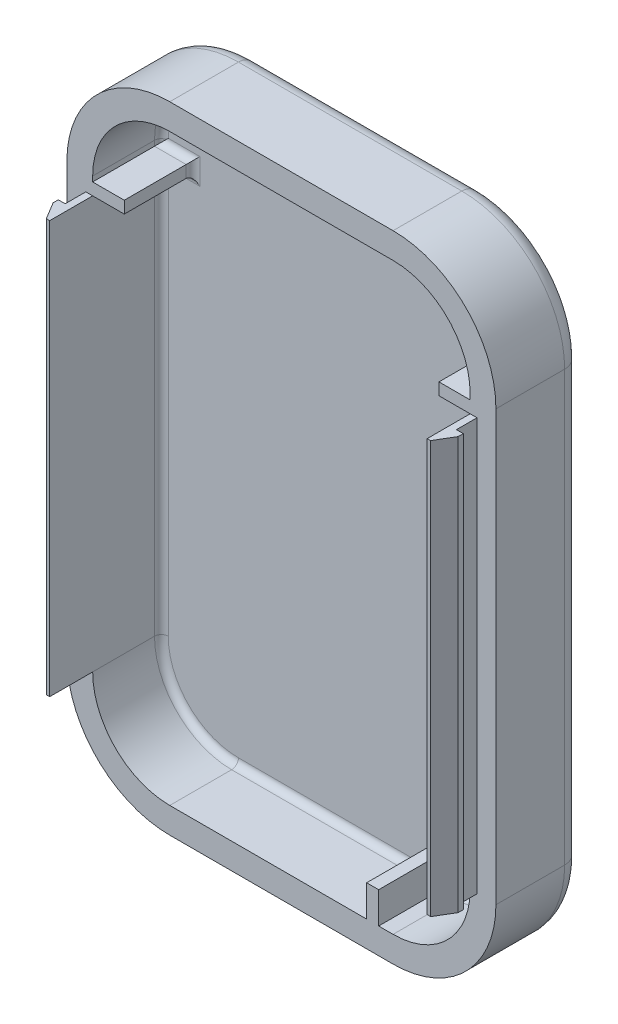
SolidWorks part; units mm, degrees
ref_plane "Front Plane" through (0, 0, 0) normal (0, 0, 1) x (1, 0, 0)
ref_plane "Top Plane" through (0, 0, 0) normal (0, 1, 0) x (1, 0, 0)
ref_plane "Right Plane" through (0, 0, 0) normal (1, 0, 0) x (0, 0, -1)
sketch "Sketch1" plane through (0, 0, 25.9804) normal (0, 0, -1) x (-1, 0, 0)
  line L15 (-18.3299, 29.3735) -> (-16.5134, 29.3735)
  line L16 (-16.5134, 29.3735) -> (-16.5134, 30.0735)
  line L17 (-16.5134, 30.0735) -> (-18.3299, 30.0735)
  line L18 (-16.2134, 29.0735) -> (-17.8299, 29.0735) construction
  line L19 (-16.2134, 30.3735) -> (-16.2134, 29.0735) construction
  line L20 (-17.8299, 30.3735) -> (-16.2134, 30.3735) construction
  line L21 (-18.3299, 30.0735) -> (-18.3299, 30.3735)
  line L22 (3.6447, 29.3735) -> (1.8044, 29.3735)
  line L23 (1.8044, 29.3735) -> (1.8044, 30.0735)
  line L24 (1.8044, 30.0735) -> (3.6447, 30.0735)
  line L25 (1.5044, 29.0735) -> (1.5044, 30.3735) construction
  line L26 (3.1447, 29.0735) -> (1.5044, 29.0735) construction
  line L27 (1.5044, 30.3735) -> (3.1447, 30.3735) construction
  line L28 (3.6447, 30.0735) -> (3.6447, 30.3735)
  line L29 (2.0044, 29.5735) -> (2.0044, 29.8735)
  line L30 (2.0044, 29.8735) -> (3.6168, 29.8735)
  line L31 (-0.8426, 34.8608) -> (-13.8426, 34.8608)
  line L32 (-18.302, 29.8735) -> (-16.7134, 29.8735)
  line L33 (-16.7134, 29.8735) -> (-16.7134, 29.5735)
  line L34 (-16.7134, 29.5735) -> (-18.3299, 29.5735)
  line L35 (-18.3299, 29.5735) -> (-18.3299, 5.3734)
  line L36 (-13.8426, 0.8861) -> (-12.8028, 0.8861)
  line L37 (-12.8028, 0.8861) -> (-12.8028, 2.5175)
  line L38 (-12.8028, 2.5175) -> (-12.5028, 2.5175)
  line L39 (-12.5028, 2.5175) -> (-12.5028, 0.8861)
  line L40 (-12.5028, 0.8861) -> (-0.8426, 0.8861)
  line L41 (3.6447, 5.3734) -> (3.6447, 29.5735)
  line L42 (3.6447, 29.5735) -> (2.0044, 29.5735)
  line L45 (-0.8426, 34.8608) -> (-13.8426, 34.8608)
  line L49 (-18.3299, 29.3735) -> (-18.3299, 5.3734)
  line L50 (-13.8426, 0.8861) -> (-13.0028, 0.8861)
  line L54 (-12.3028, 0.8861) -> (-0.8426, 0.8861)
  line L55 (3.6447, 5.3734) -> (3.6447, 29.3735)
  line L57 (-12.3028, 0.8861) -> (-12.3028, 2.7175)
  line L58 (-12.3028, 2.7175) -> (-13.0028, 2.7175)
  line L59 (-13.0028, 2.7175) -> (-13.0028, 0.8861)
  line L60 (-13.3028, 3.0175) -> (-12.0028, 3.0175) construction
  line L61 (-13.3028, 1.3861) -> (-13.3028, 3.0175) construction
  line L62 (-12.0028, 3.0175) -> (-12.0028, 1.3861) construction
  line L66 (-0.8426, 36.3608) -> (-13.8426, 36.3608)
  line L67 (-0.8426, 36.3608) -> (-13.8426, 36.3608)
  line L69 (5.1447, 5.3734) -> (5.1447, 29.0735)
  line L70 (5.1447, 5.3734) -> (5.1447, 30.3735)
  line L72 (-19.8299, 29.0735) -> (-19.8299, 5.3734)
  line L73 (-19.8299, 30.3735) -> (-19.8299, 5.3734)
  line L75 (-12.0028, -0.6139) -> (-0.8426, -0.6139)
  line L76 (-13.8426, -0.6139) -> (-0.8426, -0.6139)
  arc A6 (-13.8426, 36.3608) -> (-19.8299, 30.3735) centre (-13.8426, 30.3735) ccw
  arc A7 (-13.8426, 36.3608) -> (-19.8299, 30.3735) centre (-13.8426, 30.3735) ccw
  arc A8 (3.6168, 29.8735) -> (-0.8426, 34.8608) centre (-0.8426, 30.3735) ccw
  arc A9 (-13.8426, 34.8608) -> (-18.302, 29.8735) centre (-13.8426, 30.3735) ccw
  arc A10 (-18.3299, 5.3734) -> (-13.8426, 0.8861) centre (-13.8426, 5.3734) ccw
  arc A11 (-0.8426, 0.8861) -> (3.6447, 5.3734) centre (-0.8426, 5.3734) ccw
  arc A12 (3.6447, 30.3735) -> (-0.8426, 34.8608) centre (-0.8426, 30.3735) ccw
  arc A13 (-13.8426, 34.8608) -> (-18.3299, 30.3735) centre (-13.8426, 30.3735) ccw
  arc A14 (-18.3299, 5.3734) -> (-13.8426, 0.8861) centre (-13.8426, 5.3734) ccw
  arc A15 (-0.8426, 0.8861) -> (3.6447, 5.3734) centre (-0.8426, 5.3734) ccw
  arc A17 (5.1447, 30.3735) -> (-0.8426, 36.3608) centre (-0.8426, 30.3735) ccw
  arc A18 (5.1447, 30.3735) -> (-0.8426, 36.3608) centre (-0.8426, 30.3735) ccw
  arc A20 (-19.8299, 5.3734) -> (-13.8426, -0.6139) centre (-13.8426, 5.3734) ccw
  arc A21 (-19.8299, 5.3734) -> (-13.8426, -0.6139) centre (-13.8426, 5.3734) ccw
  arc A23 (-0.8426, -0.6139) -> (5.1447, 5.3734) centre (-0.8426, 5.3734) ccw
  arc A24 (-0.8426, -0.6139) -> (5.1447, 5.3734) centre (-0.8426, 5.3734) ccw
  dimension "D2" = 0.3
  dimension "D3" = 0.3
  dimension "D4" = 0.3
  dimension "D5" = 0.3
  dimension "D6" = 0.3
  dimension "D7" = 0.3
  dimension "D8" = 0.3
  dimension "D9" = 0.3
  dimension "D10" = 0.3
  dimension "D1" = 0.5
  dimension "D11" = 2
  dimension "D12" = 2
  dimension "D13" = 2
  dimension "D14" = 2
  dimension "D15" = 2
  dimension "D16" = 2
  dimension "D17" = 2
  dimension "D18" = 2
extrude "Boss-Extrude1" add sketch "Sketch1" along normal blind 4
sketch "Sketch2" plane through (0, 0, 21.9804) normal (0, 0, -1) x (-1, 0, 0)
  line L0 (-19.8299, 30.3735) -> (-19.8299, 5.3734) construction
  line L1 (-13.8426, -0.6139) -> (-0.8426, -0.6139) construction
  line L2 (5.1447, 5.3734) -> (5.1447, 30.3735) construction
  line L3 (-0.8426, 36.3608) -> (-13.8426, 36.3608) construction
  line L4 (-19.8299, 30.3735) -> (-19.8299, 5.3734)
  line L5 (-13.8426, -0.6139) -> (-0.8426, -0.6139)
  line L6 (5.1447, 5.3734) -> (5.1447, 30.3735)
  line L7 (-0.8426, 36.3608) -> (-13.8426, 36.3608)
  arc A0 (-19.8299, 5.3734) -> (-13.8426, -0.6139) centre (-13.8426, 5.3734) ccw construction
  arc A1 (-0.8426, -0.6139) -> (5.1447, 5.3734) centre (-0.8426, 5.3734) ccw construction
  arc A2 (5.1447, 30.3735) -> (-0.8426, 36.3608) centre (-0.8426, 30.3735) ccw construction
  arc A3 (-13.8426, 36.3608) -> (-19.8299, 30.3735) centre (-13.8426, 30.3735) ccw construction
  arc A4 (-19.8299, 5.3734) -> (-13.8426, -0.6139) centre (-13.8426, 5.3734) ccw
  arc A5 (-0.8426, -0.6139) -> (5.1447, 5.3734) centre (-0.8426, 5.3734) ccw
  arc A6 (5.1447, 30.3735) -> (-0.8426, 36.3608) centre (-0.8426, 30.3735) ccw
  arc A7 (-13.8426, 36.3608) -> (-19.8299, 30.3735) centre (-13.8426, 30.3735) ccw
extrude "Boss-Extrude2" add sketch "Sketch2" along normal blind 1
sketch "Sketch3" plane through (0, 0, 25.9804) normal (0, 0, 1) x (1, 0, 0)
  line L1 (-3.6447, 29.3735) -> (-4.4447, 29.3735)
  line L2 (-3.6447, 29.3735) -> (-3.6447, 5.3734)
  line L3 (-3.6447, 5.3734) -> (-4.4447, 5.3734)
  line L4 (-4.4447, 29.3735) -> (-4.4447, 5.3734)
  line L5 (18.3299, 29.3735) -> (19.1299, 29.3735)
  line L6 (18.3299, 29.3735) -> (18.3299, 5.3734)
  line L7 (18.3299, 5.3734) -> (19.1299, 5.3734)
  line L8 (19.1299, 29.3735) -> (19.1299, 5.3734)
  dimension "D1" = 0.8
  dimension "D2" = 0.8
extrude "Boss-Extrude3" add sketch "Sketch3" along normal blind 2.5
sketch "Sketch4" plane through (0, 5.3734, 0) normal (0, -1, 0) x (1, 0, 0)
  line L0 (-4.4447, 25.9804) -> (-4.0447, 25.9804)
  line L1 (0.8426, 25.9804) -> (-5.1447, 25.9804) construction
  line L2 (-4.0447, 25.9804) -> (-4.0447, 27.1804)
  line L3 (-4.0447, 27.1804) -> (-4.4447, 27.1804)
  line L4 (-4.4447, 28.4804) -> (-4.4447, 25.9804) construction
  line L5 (-4.4447, 27.1804) -> (-4.4447, 25.9804)
  line L6 (-4.4447, 28.4804) -> (-4.4447, 27.4804)
  line L7 (19.1299, 25.9804) -> (18.7299, 25.9804)
  line L8 (19.1299, 25.9804) -> (19.1299, 27.1804)
  line L9 (19.1299, 27.1804) -> (18.7299, 27.1804)
  line L10 (18.7299, 25.9804) -> (18.7299, 27.1804)
  line L11 (-4.4447, 27.4804) -> (-3.8447, 28.4804)
  line L12 (-4.4447, 28.4804) -> (-3.6447, 28.4804) construction
  line L13 (-3.8447, 28.4804) -> (-4.4447, 28.4804)
  line L14 (18.5299, 28.4804) -> (19.1299, 28.4804)
  line L15 (18.3299, 28.4804) -> (19.1299, 28.4804) construction
  line L16 (19.1299, 28.4804) -> (19.1299, 25.9804) construction
  line L17 (19.1299, 28.4804) -> (19.1299, 27.4804)
  line L18 (19.1299, 27.4804) -> (18.5299, 28.4804)
  dimension "D1" = 0.4
  dimension "D2" = 1.2
  dimension "D3" = 0.4
  dimension "D4" = 1.2
  dimension "D5" = 0.6
  dimension "D6" = 1
  dimension "D7" = 0.6
  dimension "D8" = 1
extrude "Cut-Extrude1" cut sketch "Sketch4" against normal up to next
fillet "Fillet1" radius 1 8 edges at (7.3426, 36.3608, 20.9804) (-3.3911, 34.6071, 20.9804) (-5.1447, 17.8735, 20.9804) (-3.3911, 1.1398, 20.9804) (7.3426, -0.6139, 20.9804) (18.0763, 1.1398, 20.9804) (19.8299, 17.8735, 20.9804) (18.0763, 34.6071, 20.9804)
fillet "Fillet2" radius 0.4 18 edges at (7.3426, 34.8608, 21.9804) (17.0156, 33.5465, 21.9804) (17.4217, 30.0735, 21.9804) (16.5134, 29.7235, 21.9804) (17.4217, 29.3735, 21.9804) (18.3299, 17.3735, 21.9804) (17.0156, 2.2004, 21.9804) (13.4227, 0.8861, 21.9804) (13.0028, 1.8018, 21.9804) (12.6528, 2.7175, 21.9804) (12.3028, 1.8018, 21.9804) (6.5727, 0.8861, 21.9804) (-2.3304, 2.2004, 21.9804) (-3.6447, 17.3735, 21.9804) (-2.7246, 29.3735, 21.9804) (-1.8044, 29.7235, 21.9804) (-2.7246, 30.0735, 21.9804) (-2.3304, 33.5465, 21.9804)
